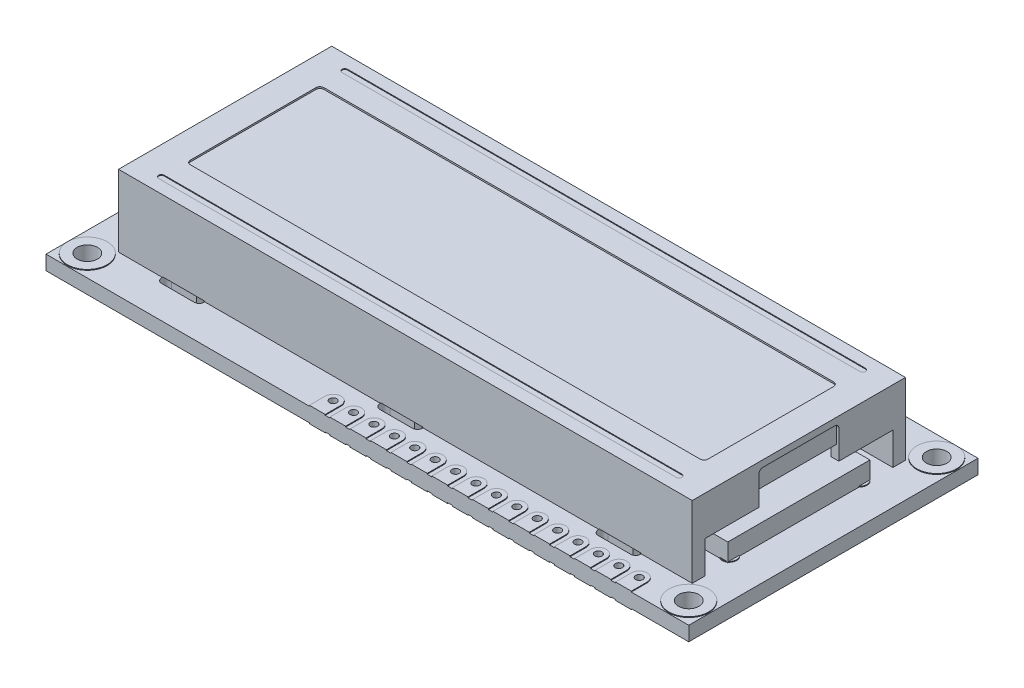
SolidWorks part; units mm, degrees
ref_plane "Front Plane" through (0, 0, 0) normal (0, 0, 1) x (1, 0, 0)
ref_plane "Top Plane" through (0, 0, 0) normal (0, 1, 0) x (1, 0, 0)
ref_plane "Right Plane" through (0, 0, 0) normal (1, 0, 0) x (0, 0, -1)
sketch "Sketch1" plane through (0, 0, 0) normal (0, 1, 0) x (1, 0, 0)
  line L5 (4.2965, 31.2697) -> (75.7035, 31.2697)
  line L6 (4.2965, 31.2697) -> (4.2965, 4.7303)
  line L7 (4.2965, 4.7303) -> (75.7035, 4.7303)
  line L8 (75.7035, 31.2697) -> (75.7035, 4.7303)
  line L9 (4.2965, 31.2697) -> (75.7035, 4.7303) construction
  line L10 (4.2965, 4.7303) -> (75.7035, 31.2697) construction
  point P5 (40, 18)
  dimension "D1" = 71.407
extrude "Boss-Extrude2" add sketch "Sketch1" along normal blind 8.93 from offset 1.79
sketch "Sketch3" plane through (0, 0, 0) normal (0, 1, 0) x (1, 0, 0)
  line L3 (40, 36) -> (80, 36)
  line L5 (0, 0) -> (80, 0)
  line L6 (0, 0) -> (0, 36)
  line L7 (0, 36) -> (80, 36)
  line L8 (80, 0) -> (80, 36)
  line L9 (0, 0) -> (80, 36) construction
  line L10 (0, 36) -> (80, 0) construction
  point P4 (0, 0)
extrude "Boss-Extrude3" add sketch "Sketch3" along normal blind 1.79 contours L5 L8 L3 L7 L6 region at (40, 0, -18)
sketch "Sketch4" plane through (0, 0, 0) normal (0, 1, 0) x (1, 0, 0)
  line L5 (7.78, 9.685) -> (72.22, 9.685)
  line L6 (7.78, 9.685) -> (7.78, 26.315)
  line L7 (7.78, 26.315) -> (72.22, 26.315)
  line L8 (72.22, 9.685) -> (72.22, 26.315)
  line L9 (7.78, 9.685) -> (72.22, 26.315) construction
  line L10 (7.78, 26.315) -> (72.22, 9.685) construction
extrude "Cut-Extrude1" cut sketch "Sketch4" against normal blind 0.2 from surface starting at face at (40, 10.72, -18)
ref_plane "Plane1" through (0, 10.72, 0) normal (0, 1, 0) x (1, 0, 0)
sketch "Sketch6" plane through (0, 10.72, 0) normal (0, 1, 0) x (1, 0, 0)
  line L4 (7.78, 29.7697) -> (72.22, 29.7697)
  line L5 (7.78, 29.0648) -> (72.22, 29.0648)
  circle A0 centre (7.78, 29.4173) radius 0.3524
  circle A1 centre (72.22, 29.4173) radius 0.3524
extrude "Cut-Extrude4" cut sketch "Sketch6" against normal blind 0.1 contours A1 L4 A0 L5 | A1 | A0 region at (40, 10.72, -29.4173) region at (7.78, 10.72, -29.4173) region at (72.22, 10.72, -29.4173)
ref_plane "Plane2" through (0, 0, -18) normal (0, 0, 1) x (1, 0, 0)
mirror "Mirror1" about plane through (0, 0, -18) normal (0, 0, 1) of "Cut-Extrude4"
fillet "Fillet1" radius 0.5 4 edges at (72.22, 10.62, -9.685) (72.22, 10.62, -26.315) (7.78, 10.62, -9.685) (7.78, 10.62, -26.315)
sketch "Sketch7" plane through (0, 0, 0) normal (1, 0, 0) x (0, 0, -1)
  line L5 (6.3, 1.79) -> (29.7, 1.79)
  line L6 (6.3, 1.79) -> (6.3, 5.83)
  line L7 (6.3, 5.83) -> (29.7, 5.83)
  line L8 (29.7, 1.79) -> (29.7, 5.83)
  line L9 (6.3, 1.79) -> (29.7, 5.83) construction
  line L10 (6.3, 5.83) -> (29.7, 1.79) construction
  point P6 (18, 3.81)
extrude "Cut-Extrude5" cut sketch "Sketch7" along normal through all contours L5 L8 L7 L6 region at (0, 3.81, -18)
ref_plane "Plane3" through (4.2965, 0, 0) normal (-1, 0, 0) x (0, 0, 1)
sketch "Sketch8" plane through (4.2965, 0, 0) normal (-1, 0, 0) x (0, 0, 1)
  line L2 (0, 1.79) -> (-36, 1.79) construction
  line L6 (-26.84, 1.79) -> (-9.155, 1.79)
  line L7 (-26.84, 1.79) -> (-26.84, 4.04)
  line L8 (-26.84, 4.04) -> (-9.155, 4.04)
  line L9 (-9.155, 1.79) -> (-9.155, 4.04)
extrude "Boss-Extrude5" add sketch "Sketch8" against normal blind 69.41 from offset 2 offset against normal yes
sketch "Sketch13" plane through (0, 4.04, 0) normal (0, 1, 0) x (1, 0, 0)
  line L0 (6.2965, 26.84) -> (6.2965, 9.155)
  line L2 (1.5, 20.9275) -> (6.2965, 26.84)
  line L5 (1.5, 20.9275) -> (1.5, 15.0675)
  line L8 (1.5, 15.0675) -> (6.2965, 9.155)
extrude "Boss-Extrude6" add sketch "Sketch13" against normal up to next
ref_plane "Plane5" through (75.7035, 0, 0) normal (1, 0, 0) x (0, 0, -1)
sketch "Sketch14" plane through (75.7035, 0, 0) normal (1, 0, 0) x (0, 0, -1)
  line L2 (18, 5.896) -> (18, -5.896) construction
  line L3 (18, 9.9) -> (13.02, 9.9)
  line L4 (18, 9.9) -> (22.98, 9.9)
  line L6 (13.02, 9.9) -> (22.98, 9.9)
  line L7 (13.02, 9.9) -> (13.02, 5.83)
  line L8 (13.02, 5.83) -> (22.98, 5.83)
  line L9 (22.98, 9.9) -> (22.98, 5.83)
extrude "Cut-Extrude6" cut sketch "Sketch14" against normal blind 0.3 contours L9 L4 L3 L7 L8 region at (75.7035, 7.865, -18)
fillet "Fillet2" radius 0.5 2 edges at (75.5535, 9.9, -22.98) (75.5535, 9.9, -13.02)
sketch "Sketch15" plane through (75.4035, 0, 0) normal (1, 0, 0) x (0, 0, -1)
  line L1 (13.02, 9.4) -> (13.02, 5.83) construction
  line L3 (13.02, 7.5) -> (22.98, 7.5)
  line L4 (13.02, 7.5) -> (13.02, 5.83)
  line L5 (13.02, 5.83) -> (22.98, 5.83)
  line L6 (22.98, 7.5) -> (22.98, 5.83)
extrude "Cut-Extrude7" cut sketch "Sketch15" against normal blind 70.4
sketch "Sketch18" plane through (75.7035, 0, 0) normal (1, 0, 0) x (0, 0, -1)
  line L2 (13.02, 9.4) -> (13.02, 5.83) construction
  line L3 (6.3, 7.5) -> (13.02, 7.5)
  line L4 (6.3, 7.5) -> (6.3, 5.83)
  line L5 (6.3, 5.83) -> (13.02, 5.83)
  line L6 (13.02, 7.5) -> (13.02, 5.83)
  line L7 (6.3, 5.83) -> (13.02, 5.83) construction
  line L8 (22.98, 5.83) -> (29.7, 5.83) construction
  line L9 (29.7, 7.5) -> (22.98, 7.5)
  line L10 (29.7, 7.5) -> (29.7, 5.83)
  line L11 (29.7, 5.83) -> (22.98, 5.83)
  line L12 (22.98, 7.5) -> (22.98, 5.83)
  line L13 (22.98, 9.4) -> (22.98, 5.83) construction
extrude "Cut-Extrude8" cut sketch "Sketch18" against normal blind 68.4 from offset 1 offset against normal yes
sketch "Sketch20" plane through (0, 0, 0) normal (0, 1, 0) x (1, 0, 0)
  circle A0 centre (2.57, 33.43) radius 2.475
  circle A1 centre (77.43, 33.43) radius 2.475
  circle A2 centre (2.57, 2.57) radius 2.475
  circle A3 centre (77.43, 2.57) radius 2.475
  point P12 (0, 0)
  point P13 (0, 0)
  point P14 (0, 0)
  point P15 (0, 0)
  point P16 (0, 0)
  point P17 (0, 0)
  point P18 (0, 0)
extrude "Boss-Extrude7" add sketch "Sketch20" along normal blind 1.99 from offset 0.1 offset against normal yes
sketch "Sketch23" plane through (0, 0, 0) normal (0, 1, 0) x (1, 0, 0)
  circle A0 centre (2.57, 33.43) radius 1.27
  circle A1 centre (77.43, 33.43) radius 1.27
  circle A2 centre (2.57, 2.57) radius 1.27
  circle A3 centre (77.43, 2.57) radius 1.27
extrude "Cut-Extrude10" cut sketch "Sketch23" against normal through all both and the other way through all
sketch "Sketch24" plane through (0, 0, 0) normal (0, 1, 0) x (1, 0, 0)
  line L0 (80, 0) -> (75.11, 0)
  line L4 (1.5, 15.0675) -> (1.5, 20.9275) construction
  line L5 (80, 0) -> (80, 36) construction
  line L6 (0, 0) -> (80, 0) construction
  line L9 (0.3, 16.1022) -> (1.5, 16.1022)
  line L10 (0.3, 16.1022) -> (0.3, 17.3067)
  line L11 (0.3, 17.3067) -> (1.5, 17.3067)
  line L12 (1.5, 16.1022) -> (1.5, 17.3067)
  line L13 (0.3, 16.1022) -> (1.5, 17.3067) construction
  line L14 (0.3, 17.3067) -> (1.5, 16.1022) construction
  circle A0 centre (0.9, 10.6) radius 0.9
  circle A1 centre (0.9, 14.2) radius 0.9
  circle A2 centre (0.9, 25.72) radius 0.9
  circle A3 centre (0.9, 21.88) radius 0.9
  circle A4 centre (0.9, 19.2833) radius 0.6
  circle A5 centre (4.85, 26.17) radius 0.9
  circle A6 centre (4.85, 9.95) radius 0.9
  circle A7 centre (75.11, 9.95) radius 0.9
  circle A8 centre (75.11, 26.17) radius 0.9
  point P22 (0.9, 16.7044)
extrude "Boss-Extrude16" add sketch "Sketch24" along normal blind 1.99 from offset 0.1 separate body contours A3 | A4 | L9 L12 L11 L10 | A1 | A6 | A0 | A7 | A8 | A2 | A5 region at (0.9, 0, -16.7044) region at (0.9, 0, -10.6) region at (0.9, 0, -14.2) region at (0.9, 0, -25.72) region at (0.9, 0, -21.88) region at (0.9, 0, -19.2833) region at (4.85, 0, -26.17) region at (4.85, 0, -9.95) region at (75.11, 0, -9.95) region at (75.11, 0, -26.17) offset against normal yes
sketch "Sketch26" plane through (0, 0, 0) normal (0, 1, 0) x (1, 0, 0)
  circle A0 centre (0.9, 25.72) radius 0.54
  circle A1 centre (0.9, 21.88) radius 0.54
  circle A2 centre (0.9, 19.2833) radius 0.45
  circle A3 centre (0.9, 16.7044) radius 0.45
  circle A4 centre (0.9, 14.2) radius 0.54
  circle A5 centre (0.9, 10.6) radius 0.54
  circle A7 centre (4.85, 9.95) radius 0.54
  circle A9 centre (4.85, 26.17) radius 0.54
  circle A11 centre (75.11, 26.17) radius 0.54
  circle A13 centre (75.11, 9.95) radius 0.54
extrude "Cut-Extrude11" cut sketch "Sketch26" along normal blind 1.99 from offset 0.1 contours A0 | A9 | A1 | A2 | A4 | A5 | A7 | A13 | A3 | A11 region at (0.9, 0, -25.72) region at (0.9, 0, -21.88) region at (0.9, 0, -19.2833) region at (0.9, 0, -14.2) region at (0.9, 0, -10.6) region at (4.85, 0, -9.95) region at (4.85, 0, -26.17) region at (75.11, 0, -9.95) offset against normal yes
sketch "Sketch27" plane through (0, 0, 0) normal (0, 1, 0) x (1, 0, 0)
  line L1 (0, 0) -> (80, 0) construction
  line L2 (72.85, 0) -> (70.8837, 0)
  line L3 (70.8837, 0) -> (70.8837, 1.97)
  line L5 (72.85, 1.97) -> (72.85, 0)
  line L6 (68.3437, 0) -> (68.3437, 1.97)
  line L7 (70.31, 1.97) -> (70.31, 0)
  line L8 (70.31, 0) -> (68.3437, 0)
  line L9 (65.8037, 0) -> (65.8037, 1.97)
  line L10 (67.77, 1.97) -> (67.77, 0)
  line L11 (67.77, 0) -> (65.8037, 0)
  line L12 (63.2637, 0) -> (63.2637, 1.97)
  line L13 (65.23, 1.97) -> (65.23, 0)
  line L14 (65.23, 0) -> (63.2637, 0)
  line L15 (60.7237, 0) -> (60.7237, 1.97)
  line L16 (62.69, 1.97) -> (62.69, 0)
  line L17 (62.69, 0) -> (60.7237, 0)
  line L18 (58.1837, 0) -> (58.1837, 1.97)
  line L19 (60.15, 1.97) -> (60.15, 0)
  line L20 (60.15, 0) -> (58.1837, 0)
  line L21 (55.6437, 0) -> (55.6437, 1.97)
  line L22 (57.61, 1.97) -> (57.61, 0)
  line L23 (57.61, 0) -> (55.6437, 0)
  line L24 (53.1037, 0) -> (53.1037, 1.97)
  line L25 (55.07, 1.97) -> (55.07, 0)
  line L26 (55.07, 0) -> (53.1037, 0)
  line L27 (50.5637, 0) -> (50.5637, 1.97)
  line L28 (52.53, 1.97) -> (52.53, 0)
  line L29 (52.53, 0) -> (50.5637, 0)
  line L30 (48.0237, 0) -> (48.0237, 1.97)
  line L31 (49.99, 1.97) -> (49.99, 0)
  line L32 (49.99, 0) -> (48.0237, 0)
  line L33 (45.4837, 0) -> (45.4837, 1.97)
  line L34 (47.45, 1.97) -> (47.45, 0)
  line L35 (47.45, 0) -> (45.4837, 0)
  line L36 (42.9437, 0) -> (42.9437, 1.97)
  line L37 (44.91, 1.97) -> (44.91, 0)
  line L38 (44.91, 0) -> (42.9437, 0)
  line L39 (40.4037, 0) -> (40.4037, 1.97)
  line L40 (42.37, 1.97) -> (42.37, 0)
  line L41 (42.37, 0) -> (40.4037, 0)
  line L42 (37.8637, 0) -> (37.8637, 1.97)
  line L43 (39.83, 1.97) -> (39.83, 0)
  line L44 (39.83, 0) -> (37.8637, 0)
  line L45 (35.3237, 0) -> (35.3237, 1.97)
  line L46 (37.29, 1.97) -> (37.29, 0)
  line L47 (37.29, 0) -> (35.3237, 0)
  line L48 (32.7837, 0) -> (32.7837, 1.97)
  line L49 (34.75, 1.97) -> (34.75, 0)
  line L50 (34.75, 0) -> (32.7837, 0)
  circle A0 centre (71.8669, 1.97) radius 0.9831
  circle A1 centre (69.3269, 1.97) radius 0.9831
  circle A2 centre (66.7869, 1.97) radius 0.9831
  circle A3 centre (64.2469, 1.97) radius 0.9831
  circle A4 centre (61.7069, 1.97) radius 0.9831
  circle A5 centre (59.1669, 1.97) radius 0.9831
  circle A6 centre (56.6269, 1.97) radius 0.9831
  circle A7 centre (54.0869, 1.97) radius 0.9831
  circle A8 centre (51.5469, 1.97) radius 0.9831
  circle A9 centre (49.0069, 1.97) radius 0.9831
  circle A10 centre (46.4669, 1.97) radius 0.9831
  circle A11 centre (43.9269, 1.97) radius 0.9831
  circle A12 centre (41.3869, 1.97) radius 0.9831
  circle A13 centre (38.8469, 1.97) radius 0.9831
  circle A14 centre (36.3069, 1.97) radius 0.9831
  circle A15 centre (33.7669, 1.97) radius 0.9831
  point P10 (0, 0)
  dimension "D1" = 16
extrude "Boss-Extrude17" add sketch "Sketch27" along normal blind 1.99 from offset 0.1 contours A15 L48 L50 L49 | A14 L45 L47 L46 | A14 | A13 L42 L44 L43 | A13 | A12 L39 L41 L40 | A12 | A11 L36 L38 L37 | A10 L33 L35 L34 | A10 | A9 L30 L32 L31 | A9 | A8 L27 L29 L28 | A8 | A7 L24 L26 L25 | A6 L21 L23 L22 | A6 | A5 | A5 L18 L20 L19 | A4 L15 L17 L16 | A3 L12 L14 L13 | A3 | A2 | A2 L9 L11 L10 | A1 L6 L8 L7 | A1 | A0 L3 L2 L5 | A7 | A15 | A11 | A4 | A0 region at (71.8669, 0, -0.619) region at (69.3269, 0, -0.619) region at (69.3269, 0, -1.97) region at (66.7869, 0, -0.619) region at (66.7869, 0, -1.97) region at (64.2469, 0, -0.619) region at (64.2469, 0, -1.97) region at (61.7069, 0, -0.619) region at (59.1669, 0, -0.619) region at (59.1669, 0, -1.97) region at (56.6269, 0, -0.619) region at (56.6269, 0, -1.97) region at (54.0869, 0, -0.619) region at (54.0869, 0, -1.97) region at (51.5469, 0, -0.619) region at (51.5469, 0, -1.97) region at (49.0069, 0, -0.619) region at (49.0069, 0, -1.97) region at (46.4669, 0, -0.619) region at (46.4669, 0, -1.97) region at (43.9269, 0, -0.619) region at (41.3869, 0, -0.619) region at (41.3869, 0, -1.97) region at (38.8469, 0, -0.619) region at (38.8469, 0, -1.97) region at (36.3069, 0, -0.619) region at (36.3069, 0, -1.97) region at (33.7669, 0, -0.619) offset against normal yes
sketch "Sketch28" plane through (0, 0, 0) normal (0, 1, 0) x (1, 0, 0)
  circle A0 centre (69.3269, 1.97) radius 0.45
  circle A1 centre (71.8669, 1.97) radius 0.45
  circle A2 centre (66.7869, 1.97) radius 0.45
  circle A3 centre (64.2469, 1.97) radius 0.45
  circle A4 centre (61.7069, 1.97) radius 0.45
  circle A5 centre (59.1669, 1.97) radius 0.45
  circle A6 centre (56.6269, 1.97) radius 0.45
  circle A7 centre (54.0869, 1.97) radius 0.45
  circle A8 centre (51.5469, 1.97) radius 0.45
  circle A9 centre (49.0069, 1.97) radius 0.45
  circle A10 centre (46.4669, 1.97) radius 0.45
  circle A11 centre (43.9269, 1.97) radius 0.45
  circle A12 centre (41.3869, 1.97) radius 0.45
  circle A13 centre (38.8469, 1.97) radius 0.45
  circle A14 centre (36.3069, 1.97) radius 0.45
  circle A15 centre (33.7669, 1.97) radius 0.45
  point P1 (0, 0)
  dimension "D1" = 16
extrude "Cut-Extrude12" cut sketch "Sketch28" against normal through all both and the other way through all contours A14 | A13 | A12 | A11 | A10 | A8 | A7 | A6 | A5 | A4 | A3 | A2 | A0 | A1 | A15 | A9 region at (69.3269, 0, -1.97) region at (71.8669, 0, -1.97) region at (66.7869, 0, -1.97) region at (64.2469, 0, -1.97) region at (61.7069, 0, -1.97) region at (59.1669, 0, -1.97) region at (56.6269, 0, -1.97) region at (54.0869, 0, -1.97) region at (51.5469, 0, -1.97) region at (46.4669, 0, -1.97) region at (43.9269, 0, -1.97) region at (41.3869, 0, -1.97) region at (38.8469, 0, -1.97) region at (36.3069, 0, -1.97)
ref_plane "Plane6" through (0, 0, 0) normal (0, -1, 0) x (-1, 0, 0)
sketch "Sketch29" plane through (0, 0, 0) normal (0, -1, 0) x (-1, 0, 0)
  line L0 (-80, 36) -> (-69.36, 36)
  line L2 (-68.81, 27.3375) -> (-68.81, 25.7375)
  line L3 (-73.1, 23.05) -> (-74.7, 23.05)
  line L4 (-73.1, 23.05) -> (-73.1, 24.2)
  line L5 (-73.1, 24.2) -> (-74.7, 24.2)
  line L6 (-75.5, 23.05) -> (-77.1, 23.05)
  line L7 (-75.5, 23.05) -> (-75.5, 24.2)
  line L8 (-75.5, 24.2) -> (-77.1, 24.2)
  line L9 (-77.1, 23.05) -> (-77.1, 24.2)
  line L10 (-74.7, 23.05) -> (-74.7, 24.2)
  line L11 (-73.1, 21.1) -> (-74.7, 21.1)
  line L12 (-73.1, 21.1) -> (-73.1, 22.25)
  line L13 (-73.1, 22.25) -> (-74.7, 22.25)
  line L14 (-75.5, 21.1) -> (-77.1, 21.1)
  line L15 (-75.5, 21.1) -> (-75.5, 22.25)
  line L16 (-75.5, 22.25) -> (-77.1, 22.25)
  line L17 (-77.1, 21.1) -> (-77.1, 22.25)
  line L18 (-74.7, 21.1) -> (-74.7, 22.25)
  line L19 (-73.1, 19.15) -> (-74.7, 19.15)
  line L20 (-73.1, 19.15) -> (-73.1, 20.3)
  line L21 (-73.1, 20.3) -> (-74.7, 20.3)
  line L22 (-75.5, 19.15) -> (-77.1, 19.15)
  line L23 (-75.5, 19.15) -> (-75.5, 20.3)
  line L24 (-75.5, 20.3) -> (-77.1, 20.3)
  line L25 (-77.1, 19.15) -> (-77.1, 20.3)
  line L26 (-74.7, 19.15) -> (-74.7, 20.3)
  line L27 (-68.81, 27.3375) -> (-69.96, 27.3375)
  line L28 (-69.96, 27.3375) -> (-69.96, 25.7375)
  line L29 (-68.81, 24.9375) -> (-68.81, 23.3375)
  line L30 (-68.81, 24.9375) -> (-69.96, 24.9375)
  line L31 (-69.96, 24.9375) -> (-69.96, 23.3375)
  line L32 (-68.81, 23.3375) -> (-69.96, 23.3375)
  line L33 (-68.81, 25.7375) -> (-69.96, 25.7375)
  line L34 (0, 36) -> (-80, 36) construction
  line L35 (-25.55, 21.62) -> (-27.15, 21.62)
  line L36 (-25.55, 21.62) -> (-25.55, 22.77)
  line L37 (-25.55, 22.77) -> (-27.15, 22.77)
  line L38 (-27.95, 21.62) -> (-29.55, 21.62)
  line L39 (-27.95, 21.62) -> (-27.95, 22.77)
  line L40 (-27.95, 22.77) -> (-29.55, 22.77)
  line L41 (-29.55, 21.62) -> (-29.55, 22.77)
  line L42 (-27.15, 21.62) -> (-27.15, 22.77)
  line L43 (-15.0314, 29.08) -> (-9.7371, 29.08)
  line L44 (-25.55, 19.67) -> (-27.15, 19.67)
  line L45 (-25.55, 19.67) -> (-25.55, 20.82)
  line L46 (-25.55, 20.82) -> (-27.15, 20.82)
  line L47 (-27.95, 19.67) -> (-29.55, 19.67)
  line L48 (-27.95, 19.67) -> (-27.95, 20.82)
  line L49 (-27.95, 20.82) -> (-29.55, 20.82)
  line L50 (-29.55, 19.67) -> (-29.55, 20.82)
  line L51 (-27.15, 19.67) -> (-27.15, 20.82)
  line L52 (-25.55, 17.72) -> (-27.15, 17.72)
  line L53 (-25.55, 17.72) -> (-25.55, 18.87)
  line L54 (-25.55, 18.87) -> (-27.15, 18.87)
  line L55 (-27.95, 17.72) -> (-29.55, 17.72)
  line L56 (-27.95, 17.72) -> (-27.95, 18.87)
  line L57 (-27.95, 18.87) -> (-29.55, 18.87)
  line L58 (-29.55, 17.72) -> (-29.55, 18.87)
  line L59 (-27.15, 17.72) -> (-27.15, 18.87)
  line L60 (-42.1957, 29.08) -> (-36.9014, 29.08)
  line L61 (-69.36, 29.08) -> (-64.0657, 29.08)
  line L62 (-69.36, 29.08) -> (-69.36, 30.4457)
  line L63 (-69.36, 30.4457) -> (-64.0657, 30.4457)
  line L64 (-64.0657, 29.08) -> (-64.0657, 30.4457)
  line L65 (-42.1957, 29.08) -> (-42.1957, 30.4457)
  line L66 (-42.1957, 30.4457) -> (-36.9014, 30.4457)
  line L67 (-36.9014, 29.08) -> (-36.9014, 30.4457)
  line L68 (-15.0314, 29.08) -> (-15.0314, 30.4457)
  line L69 (-15.0314, 30.4457) -> (-9.7371, 30.4457)
  line L70 (-9.7371, 29.08) -> (-9.7371, 30.4457)
  line L71 (-42.1957, 5.49) -> (-36.9014, 5.49)
  line L72 (-15.0314, 5.49) -> (-9.7371, 5.49)
  line L73 (-15.0314, 5.49) -> (-15.0314, 6.8557)
  line L74 (-15.0314, 6.8557) -> (-9.7371, 6.8557)
  line L75 (-9.7371, 5.49) -> (-9.7371, 6.8557)
  line L76 (-7.27, 21.25) -> (-7.27, 22.95)
  line L77 (-7.27, 14.07) -> (-7.27, 15.77)
  line L78 (-74.13, 14.91) -> (-75.59, 14.91)
  line L79 (-74.13, 14.91) -> (-74.13, 16.12)
  line L80 (-76.19, 14.91) -> (-77.65, 14.91)
  line L81 (-76.19, 14.91) -> (-76.19, 16.12)
  line L82 (-76.19, 16.12) -> (-77.65, 16.12)
  line L83 (-77.65, 14.91) -> (-77.65, 16.12)
  line L84 (-74.13, 16.12) -> (-75.59, 16.12)
  line L85 (-75.59, 14.91) -> (-75.59, 16.12)
  line L86 (-12.2, 13) -> (-12.2, 14.7)
  line L87 (-12.2, 13) -> (-14.2, 13)
  line L88 (-14.2, 13) -> (-14.2, 14.7)
  line L89 (-14.2, 14.7) -> (-12.2, 14.7)
  line L90 (-7.27, 14.07) -> (-9.27, 14.07)
  line L91 (-12.2, 16.2) -> (-12.2, 17.9)
  line L92 (-12.2, 16.2) -> (-14.2, 16.2)
  line L93 (-14.2, 16.2) -> (-14.2, 17.9)
  line L94 (-14.2, 17.9) -> (-12.2, 17.9)
  line L95 (-9.27, 14.07) -> (-9.27, 15.77)
  line L96 (-9.27, 15.77) -> (-7.27, 15.77)
  line L97 (-7.27, 17.27) -> (-7.27, 18.97)
  line L98 (-7.27, 17.27) -> (-9.27, 17.27)
  line L99 (-9.27, 17.27) -> (-9.27, 18.97)
  line L100 (-9.27, 18.97) -> (-7.27, 18.97)
  line L101 (-7.27, 21.25) -> (-9.27, 21.25)
  line L102 (-9.27, 21.25) -> (-9.27, 22.95)
  line L103 (-9.27, 22.95) -> (-7.27, 22.95)
  line L104 (-7.27, 24.45) -> (-7.27, 26.15)
  line L105 (-7.27, 24.45) -> (-9.27, 24.45)
  line L106 (-9.27, 24.45) -> (-9.27, 26.15)
  line L107 (-9.27, 26.15) -> (-7.27, 26.15)
  line L108 (-42.1957, 5.49) -> (-42.1957, 6.8557)
  line L109 (-42.1957, 6.8557) -> (-36.9014, 6.8557)
  line L110 (-36.9014, 5.49) -> (-36.9014, 6.8557)
  line L111 (-69.36, 5.49) -> (-64.0657, 5.49)
  line L112 (-69.36, 5.49) -> (-69.36, 6.8557)
  line L113 (-69.36, 6.8557) -> (-64.0657, 6.8557)
  line L114 (-64.0657, 5.49) -> (-64.0657, 6.8557)
  circle A0 centre (-4.85, 14.85) radius 0.99
  circle A1 centre (-4.85, 21.86) radius 0.99
extrude "Boss-Extrude18" add sketch "Sketch29" along normal blind 0.1 contours A0 | L96 L95 L90 L77 | L100 L99 L98 L97 | L94 L93 L92 L91 | L89 L88 L87 L86 | L103 L102 L101 L76 | L107 L106 L105 L104 | A1 | L43 L70 L69 L68 | L59 L52 L53 L54 | L51 L44 L45 L46 | L42 L35 L36 L37 | L41 L38 L39 L40 | L50 L47 L48 L49 | L58 L55 L56 L57 | L61 L64 L63 L62 | L33 L2 L27 L28 | L10 L3 L4 L5 | L9 L6 L7 L8 | L17 L14 L15 L16 | L18 L11 L12 L13 | L26 L19 L20 L21 | L25 L22 L23 L24 | L83 L80 L81 L82 | L111 L114 L113 L112 | L72 L75 L74 L73 | L60 L67 L66 L65 | L29 L32 L31 L30 | L85 L84 L79 L78 | L71 L110 L109 L108 region at (69.385, 0, -26.5375) region at (73.9, 0, -23.625) region at (76.3, 0, -23.625) region at (73.9, 0, -21.675) region at (76.3, 0, -21.675) region at (73.9, 0, -19.725) region at (76.3, 0, -19.725) region at (26.35, 0, -22.195) region at (28.75, 0, -22.195) region at (12.3843, 0, -29.7629) region at (26.35, 0, -20.245) region at (28.75, 0, -20.245) region at (26.35, 0, -18.295) region at (28.75, 0, -18.295) region at (66.7129, 0, -29.7629) region at (8.27, 0, -22.1) region at (8.27, 0, -14.92) region at (76.92, 0, -15.515) region at (13.2, 0, -13.85) region at (13.2, 0, -17.05) region at (8.27, 0, -18.12) region at (8.27, 0, -25.3) region at (66.7129, 0, -6.1729) region at (4.85, 0, -14.85) region at (4.85, 0, -21.86)
sketch "Sketch30" plane through (0, 0, 0) normal (0, -1, 0) x (-1, 0, 0)
  circle A0 centre (-4.85, 14.85) radius 0.375
  circle A1 centre (-4.85, 21.86) radius 0.375
  point P4 (0, 0)
extrude "Cut-Extrude13" cut sketch "Sketch30" against normal blind 1.97 from offset 0.1 contours A1 | A0 region at (4.85, 0, -21.86)
sketch "Sketch31" plane through (0, -0.1, 0) normal (0, -1, 0) x (-1, 0, 0)
  line L0 (-10.3623, 5.2851) -> (-14.4063, 5.2851)
  line L1 (-37.5266, 31.9009) -> (-41.5706, 31.9009)
  line L2 (-10.3623, 4.0349) -> (-14.4063, 4.0349)
  line L3 (-37.5266, 30.6506) -> (-41.5706, 30.6506)
  line L5 (-64.6909, 5.2851) -> (-68.7349, 5.2851)
  line L6 (-10.3623, 31.9009) -> (-14.4063, 31.9009)
  line L7 (-10.3623, 30.6506) -> (-14.4063, 30.6506)
  line L8 (-64.6909, 31.9009) -> (-68.7349, 31.9009)
  line L9 (-64.6909, 30.6506) -> (-68.7349, 30.6506)
  line L10 (-37.5266, 5.2851) -> (-41.5706, 5.2851)
  line L11 (-37.5266, 4.0349) -> (-41.5706, 4.0349)
  line L12 (-64.6909, 4.0349) -> (-68.7349, 4.0349)
  circle A0 centre (-10.3623, 4.66) radius 0.6251
  circle A1 centre (-14.4063, 4.66) radius 0.6251
  circle A2 centre (-10.3623, 31.2757) radius 0.6251
  circle A3 centre (-14.4063, 31.2757) radius 0.6251
  circle A4 centre (-37.5266, 31.2757) radius 0.6251
  circle A5 centre (-41.5706, 31.2757) radius 0.6251
  circle A6 centre (-64.6909, 31.2757) radius 0.6251
  circle A7 centre (-68.7349, 31.2757) radius 0.6251
  circle A8 centre (-37.5266, 4.66) radius 0.6251
  circle A9 centre (-41.5706, 4.66) radius 0.6251
  circle A10 centre (-64.6909, 4.66) radius 0.6251
  circle A11 centre (-68.7349, 4.66) radius 0.6251
extrude "Cut-Extrude14" cut sketch "Sketch31" against normal blind 1.97 contours A1 L2 A0 L0 | A0 | A1 | A3 L7 A2 L6 | A3 | A2 | A4 | A5 L3 A4 L1 | A5 | A6 | A7 L9 A6 L8 | A7 | A9 L11 A8 L10 | A8 | A9 | A11 L12 A10 L5 | A11 | A10 region at (12.3843, -0.1, -4.66) region at (10.3623, -0.1, -4.66) region at (14.4063, -0.1, -4.66) region at (39.5486, -0.1, -31.2757) region at (37.5266, -0.1, -31.2757) region at (41.5706, -0.1, -31.2757) region at (66.7129, -0.1, -4.66) region at (64.6909, -0.1, -4.66) region at (68.7349, -0.1, -4.66) region at (12.3843, -0.1, -31.2757) region at (10.3623, -0.1, -31.2757) region at (14.4063, -0.1, -31.2757) region at (66.7129, -0.1, -31.2757) region at (64.6909, -0.1, -31.2757) region at (68.7349, -0.1, -31.2757) region at (39.5486, -0.1, -4.66) region at (37.5266, -0.1, -4.66) region at (41.5706, -0.1, -4.66)
sketch "Sketch40" plane through (0, 0, -18) normal (0, 0, 1) x (1, 0, 0)
  line L0 (1.5, 2.915) -> (0.9, 2.915)
  line L1 (1.5, 1.79) -> (1.5, 4.04) construction
  line L2 (0.9, 2.915) -> (0.9, -0.1)
  line L3 (0.095, -0.1) -> (5.045, -0.1) construction
extrude "Extrude-Thin1" add sketch "Sketch40" along normal mid plane 0.75 from offset 1.29 thin thin type one direction wall 0.2
fillet "Fillet3" radius 0.2 1 edges at (0.7, 3.115, -16.71)
pattern_linear "LPattern1" count 2 spacing 2.58 along (0, 0, -1) of "Extrude-Thin1", "Fillet3"
sketch "Sketch41" plane through (0, 0, 0) normal (0, -1, 0) x (-1, 0, 0)
  line L0 (-41.5706, 30.772) -> (-41.1039, 31.2387)
  line L1 (-41.5706, 5.228) -> (-41.1039, 4.7613)
  line L2 (-41.1039, 4.7613) -> (-40.6372, 5.228)
  line L3 (-40.6372, 5.228) -> (-41.5706, 5.228)
  line L4 (-68.7349, 5.228) -> (-68.2682, 4.7613)
  line L5 (-41.1039, 31.2387) -> (-40.6372, 30.772)
  line L9 (-68.7349, 30.772) -> (-68.2682, 31.2387)
  line L10 (-68.2682, 31.2387) -> (-67.8015, 30.772)
  line L11 (-14.4063, 5.228) -> (-13.9396, 4.7613)
  line L12 (-13.9396, 4.7613) -> (-13.4729, 5.228)
  line L13 (-13.4729, 5.228) -> (-14.4063, 5.228)
  line L14 (-68.2682, 4.7613) -> (-67.8015, 5.228)
  line L15 (-40.6372, 30.772) -> (-41.5706, 30.772)
  line L16 (-14.4063, 30.772) -> (-13.9396, 31.2387)
  line L17 (-13.9396, 31.2387) -> (-13.4729, 30.772)
  line L18 (-41.5706, 5.228) -> (-41.0713, 5.228)
  line L19 (-13.4729, 30.772) -> (-14.4063, 30.772)
  line L20 (-67.8015, 30.772) -> (-68.7349, 30.772)
  line L26 (-67.8015, 5.228) -> (-68.7349, 5.228)
  line L28 (-14.4063, 30.772) -> (-13.907, 30.772)
extrude "Boss-Extrude19" add sketch "Sketch41" against normal blind 1.89 from offset 0.1 separate body contours L12 L13 L11 | L20 L10 L9 | L19 L17 L16 | L1 L2 L3 | L4 L14 L26 | L15 L0 L5 region at (68.2682, 0, -30.9276) region at (13.9396, 0, -5.0724) region at (13.9396, 0, -30.9276)
sketch "Sketch42" plane through (0, 0, 0) normal (0, -1, 0) x (-1, 0, 0)
  line L0 (-12.3843, 6.3166) -> (-13.9396, 4.7613)
  line L1 (-14.4063, 5.228) -> (-12.8509, 6.7833)
  line L2 (-12.8509, 6.7833) -> (-12.3843, 6.3166)
  line L3 (-13.9396, 4.7613) -> (-14.4063, 5.228)
  line L4 (-39.5466, 6.3166) -> (-41.1019, 4.7613)
  line L5 (-41.5686, 5.228) -> (-40.0132, 6.7833)
  line L6 (-40.0132, 6.7833) -> (-39.5466, 6.3166)
  line L7 (-41.1019, 4.7613) -> (-41.5686, 5.228)
  line L8 (-66.7128, 6.3166) -> (-68.2682, 4.7613)
  line L9 (-68.7349, 5.228) -> (-67.1795, 6.7833)
  line L10 (-67.1795, 6.7833) -> (-66.7128, 6.3166)
  line L11 (-68.2682, 4.7613) -> (-68.7349, 5.228)
  line L12 (-13.9396, 31.2387) -> (-12.384, 29.6831)
  line L13 (-13.9396, 31.2387) -> (-14.4063, 30.772)
  line L14 (-14.4063, 30.772) -> (-12.8509, 29.2167)
  line L15 (-12.8509, 29.2167) -> (-12.384, 29.6831)
  line L16 (-41.1019, 31.2387) -> (-39.5463, 29.6831)
  line L17 (-41.1019, 31.2387) -> (-41.5686, 30.772)
  line L18 (-41.5686, 30.772) -> (-40.0132, 29.2167)
  line L19 (-40.0132, 29.2167) -> (-39.5463, 29.6831)
  line L20 (-68.2682, 31.2387) -> (-66.7125, 29.6831)
  line L21 (-68.2682, 31.2387) -> (-68.7349, 30.772)
  line L22 (-68.7349, 30.772) -> (-67.1795, 29.2167)
  line L23 (-67.1795, 29.2167) -> (-66.7125, 29.6831)
extrude "Boss-Extrude20" add sketch "Sketch42" along normal blind 1.79 from offset 0.1
fillet "Fillet4" radius 0.2 12 edges at (12.6175, -1.89, -29.4499) (14.1729, -1.89, -31.0054) (39.7798, -1.89, -29.4499) (41.3352, -1.89, -31.0054) (66.946, -1.89, -29.4499) (68.5015, -1.89, -31.0054) (66.9462, -1.89, -6.55) (68.5015, -1.89, -4.9946) (41.3352, -1.89, -4.9946) (39.7799, -1.89, -6.55) (14.1729, -1.89, -4.9946) (12.6176, -1.89, -6.55)
sketch "Sketch43" plane through (0, -0.1, 0) normal (0, -1, 0) x (-1, 0, 0)
  line L0 (-73.1, 19.15) -> (-74.7, 19.15) construction
  line L1 (-73.9, 19.15) -> (-74.3989, 19.15)
  line L2 (-73.9, 19.15) -> (-73.9, 20.3)
  line L3 (-73.9, 20.3) -> (-74.3989, 20.3)
  line L4 (-74.3989, 19.15) -> (-74.3989, 20.3)
  line L5 (-73.1, 20.3) -> (-74.7, 20.3) construction
  line L6 (-75.5, 19.15) -> (-77.1, 19.15) construction
  line L7 (-76.3, 19.15) -> (-75.8041, 19.15)
  line L8 (-76.3, 19.15) -> (-76.3, 20.3)
  line L9 (-76.3, 20.3) -> (-75.8041, 20.3)
  line L10 (-75.8041, 19.15) -> (-75.8041, 20.3)
  line L11 (-75.5, 20.3) -> (-77.1, 20.3) construction
  line L12 (-73.9, 21.1036) -> (-74.3989, 21.1036)
  line L13 (-73.9, 21.1036) -> (-73.9, 22.2536)
  line L14 (-73.9, 22.2536) -> (-74.3989, 22.2536)
  line L15 (-74.3989, 21.1036) -> (-74.3989, 22.2536)
  line L16 (-76.3, 21.1036) -> (-75.8041, 21.1036)
  line L17 (-76.3, 21.1036) -> (-76.3, 22.2536)
  line L18 (-76.3, 22.2536) -> (-75.8041, 22.2536)
  line L19 (-75.8041, 21.1036) -> (-75.8041, 22.2536)
  line L20 (-73.9, 23.0452) -> (-74.3989, 23.0452)
  line L21 (-73.9, 23.0452) -> (-73.9, 24.1952)
  line L22 (-73.9, 24.1952) -> (-74.3989, 24.1952)
  line L23 (-74.3989, 23.0452) -> (-74.3989, 24.1952)
  line L24 (-76.3, 23.0452) -> (-75.8041, 23.0452)
  line L25 (-76.3, 23.0452) -> (-76.3, 24.1952)
  line L26 (-76.3, 24.1952) -> (-75.8041, 24.1952)
  line L27 (-75.8041, 23.0452) -> (-75.8041, 24.1952)
  line L28 (-26.3748, 17.72) -> (-26.8737, 17.72)
  line L29 (-26.3748, 17.72) -> (-26.3748, 18.87)
  line L30 (-26.3748, 18.87) -> (-26.8737, 18.87)
  line L31 (-26.8737, 17.72) -> (-26.8737, 18.87)
  line L32 (-28.7748, 17.72) -> (-28.2789, 17.72)
  line L33 (-28.7748, 17.72) -> (-28.7748, 18.87)
  line L34 (-28.7748, 18.87) -> (-28.2789, 18.87)
  line L35 (-28.2789, 17.72) -> (-28.2789, 18.87)
  line L36 (-26.35, 19.67) -> (-26.8489, 19.67)
  line L37 (-26.35, 19.67) -> (-26.35, 20.82)
  line L38 (-26.35, 20.82) -> (-26.8489, 20.82)
  line L39 (-26.8489, 19.67) -> (-26.8489, 20.82)
  line L40 (-28.75, 19.67) -> (-28.2541, 19.67)
  line L41 (-28.75, 19.67) -> (-28.75, 20.82)
  line L42 (-28.75, 20.82) -> (-28.2541, 20.82)
  line L43 (-28.2541, 19.67) -> (-28.2541, 20.82)
  line L44 (-26.35, 21.62) -> (-26.8489, 21.62)
  line L45 (-26.35, 21.62) -> (-26.35, 22.77)
  line L46 (-26.35, 22.77) -> (-26.8489, 22.77)
  line L47 (-26.8489, 21.62) -> (-26.8489, 22.77)
  line L48 (-28.75, 21.62) -> (-28.2541, 21.62)
  line L49 (-28.75, 21.62) -> (-28.75, 22.77)
  line L50 (-28.75, 22.77) -> (-28.2541, 22.77)
  line L51 (-28.2541, 21.62) -> (-28.2541, 22.77)
extrude "Boss-Extrude21" add sketch "Sketch43" along normal blind 1
sketch "Sketch44" plane through (0, 0, 0) normal (0, -1, 0) x (-1, 0, 0)
  line L0 (-74.3989, 22.2593) -> (-75.8041, 22.2593)
  line L1 (-74.3989, 24.2026) -> (-75.8041, 24.2026)
  line L2 (-74.3989, 24.2026) -> (-74.3989, 23.0377)
  line L3 (-26.8489, 20.8275) -> (-28.2541, 20.8275)
  line L4 (-26.8489, 20.8275) -> (-26.8489, 19.6625)
  line L5 (-26.8489, 19.6625) -> (-28.2541, 19.6625)
  line L6 (-26.8489, 22.7775) -> (-28.2541, 22.7775)
  line L7 (-28.2541, 20.8275) -> (-28.2541, 19.6625)
  line L8 (-26.8489, 20.8275) -> (-28.2541, 19.6625) construction
  line L9 (-74.3989, 22.2593) -> (-74.3989, 21.0943)
  line L10 (-74.3989, 20.3075) -> (-75.8041, 20.3075)
  line L11 (-74.3989, 20.3075) -> (-74.3989, 19.1425)
  line L12 (-74.3989, 19.1425) -> (-75.8041, 19.1425)
  line L13 (-75.8041, 20.3075) -> (-75.8041, 19.1425)
  line L14 (-74.3989, 20.3075) -> (-75.8041, 19.1425) construction
  line L15 (-74.3989, 19.1425) -> (-75.8041, 20.3075) construction
  line L16 (-74.3989, 21.0943) -> (-75.8041, 21.0943)
  line L17 (-75.8041, 22.2593) -> (-75.8041, 21.0943)
  line L18 (-74.3989, 22.2593) -> (-75.8041, 21.0943) construction
  line L19 (-74.3989, 21.0943) -> (-75.8041, 22.2593) construction
  line L20 (-74.3989, 23.0377) -> (-75.8041, 23.0377)
  line L21 (-75.8041, 24.2026) -> (-75.8041, 23.0377)
  line L22 (-74.3989, 24.2026) -> (-75.8041, 23.0377) construction
  line L23 (-74.3989, 23.0377) -> (-75.8041, 24.2026) construction
  line L24 (-26.8489, 22.7775) -> (-26.8489, 21.6125)
  line L25 (-26.8489, 21.6125) -> (-28.2541, 21.6125)
  line L31 (-26.8737, 18.8775) -> (-28.2789, 18.8775)
  line L32 (-26.8737, 18.8775) -> (-26.8737, 17.7125)
  line L33 (-26.8737, 17.7125) -> (-28.2789, 17.7125)
  line L34 (-28.2789, 18.8775) -> (-28.2789, 17.7125)
  line L35 (-26.8737, 18.8775) -> (-28.2789, 17.7125) construction
  line L36 (-26.8737, 17.7125) -> (-28.2789, 18.8775) construction
  line L37 (-26.8489, 19.6625) -> (-28.2541, 20.8275) construction
  line L38 (-28.2541, 22.7775) -> (-28.2541, 21.6125)
  line L39 (-26.8489, 22.7775) -> (-28.2541, 21.6125) construction
  line L40 (-26.8489, 21.6125) -> (-28.2541, 22.7775) construction
  point P18 (-75.1015, 19.725)
extrude "Boss-Extrude22" add sketch "Sketch44" along normal blind 1.2
sketch "Sketch45" plane through (0, 0, 0) normal (0, -1, 0) x (-1, 0, 0)
  line L0 (-7.27, 21.25) -> (-7.27, 22.95) construction
  line L1 (-7.27, 22.1) -> (-9.27, 22.1)
  line L2 (-7.27, 22.1) -> (-7.27, 22.3069)
  line L3 (-7.27, 22.3069) -> (-9.27, 22.3069)
  line L4 (-9.27, 22.1) -> (-9.27, 22.3069)
  line L5 (-9.27, 21.25) -> (-9.27, 22.95) construction
  line L7 (-7.27, 25.0931) -> (-9.27, 25.0931)
  line L8 (-7.27, 25.0931) -> (-7.27, 25.3)
  line L9 (-7.27, 25.3) -> (-9.27, 25.3)
  line L10 (-9.27, 25.0931) -> (-9.27, 25.3)
extrude "Boss-Extrude23" add sketch "Sketch45" along normal blind 1
sketch "Sketch47" plane through (0, 0, 0) normal (0, -1, 0) x (-1, 0, 0)
  line L4 (-7.2526, 25.0931) -> (-9.2874, 25.0931)
  line L5 (-7.2526, 25.0931) -> (-7.2526, 22.3069)
  line L6 (-7.2526, 22.3069) -> (-9.2874, 22.3069)
  line L7 (-9.2874, 25.0931) -> (-9.2874, 22.3069)
  line L8 (-7.2526, 25.0931) -> (-9.2874, 22.3069) construction
  line L9 (-7.2526, 22.3069) -> (-9.2874, 25.0931) construction
  point P6 (-8.27, 23.7)
extrude "Boss-Extrude24" add sketch "Sketch47" along normal blind 1.1
sketch "Sketch48" plane through (0, 0, 0) normal (0, -1, 0) x (-1, 0, 0)
  circle A0 centre (-20, 19.25) radius 5.25
  circle A1 centre (-57.6, 19.25) radius 6.5
extrude "Boss-Extrude25" add sketch "Sketch48" along normal blind 2
fillet "Fillet5" radius 7.49 1 edges at (20, -2, -24.5)
fillet "Fillet6" radius 11 1 edges at (57.6, -2, -25.75)
